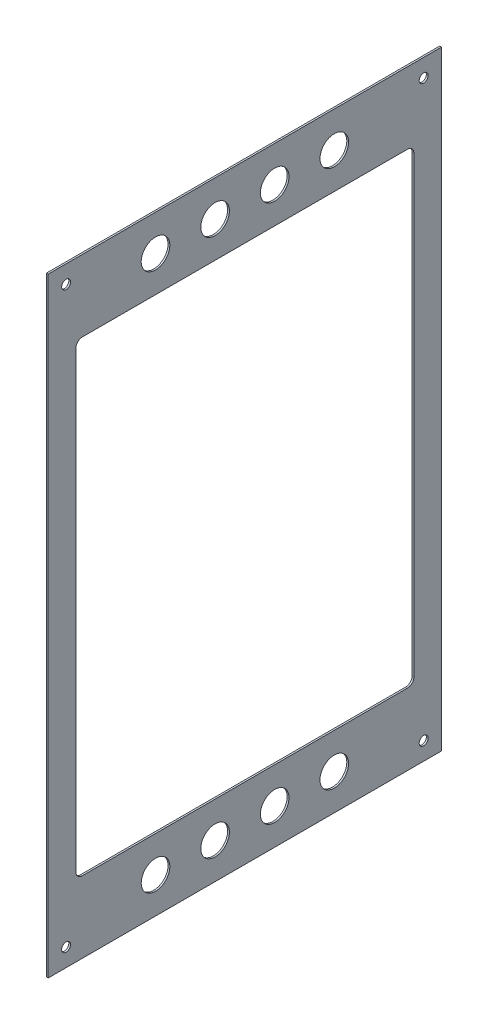
SolidWorks part; units mm, degrees
ref_plane "Front Plane" through (0, 0, 0) normal (1, 0, 0) x (0, 1, 0)
ref_plane "Top Plane" through (0, 0, 0) normal (0, 0, 1) x (0, 1, 0)
ref_plane "Right Plane" through (0, 0, 0) normal (0, 1, 0) x (-1, 0, 0)
sketch "Sketch1" plane through (0, 0, 0) normal (1, 0, 0) x (0, 1, 0)
  line L1 (-170.5, -110) -> (170.5, -110)
  line L2 (-170.5, -110) -> (-170.5, 110)
  line L3 (-170.5, 110) -> (170.5, 110)
  line L4 (170.5, -110) -> (170.5, 110)
  line L5 (-170.5, -110) -> (170.5, 110) construction
  line L6 (-170.5, 110) -> (170.5, -110) construction
  point P0 (0, 0)
  dimension "D1" = 341
  dimension "D2" = 220
extrude "Boss-Extrude1" add sketch "Sketch1" along normal blind 1
sketch "Sketch2" plane through (1, 0, 0) normal (1, 0, 0) x (0, 1, 0)
  line L8 (-170.5, 0) -> (170.5, 0) construction
  line L9 (-170.5, 110) -> (-170.5, -110) construction
  line L10 (170.5, -110) -> (170.5, 110) construction
  line L11 (150.5026, 110) -> (150.5026, -110) construction
  line L12 (-130.5026, 91.0027) -> (-130.5026, -91.0027)
  line L13 (-127.0027, -94.5026) -> (127.0027, -94.5026)
  line L14 (130.5026, -91.0027) -> (130.5026, 91.0027)
  line L15 (127.0027, 94.5026) -> (-127.0027, 94.5026)
  line L16 (-130.5026, 91.0027) -> (-130.5026, -91.0027)
  line L17 (-127.0027, -94.5026) -> (127.0027, -94.5026)
  line L18 (130.5026, -91.0027) -> (130.5026, 91.0027)
  line L19 (127.0027, 94.5026) -> (-127.0027, 94.5026)
  line L20 (170.5, 110) -> (-170.5, 110) construction
  line L21 (0, 110) -> (0, -110) construction
  line L22 (-170.5, -110) -> (170.5, -110) construction
  circle A0 centre (150.5026, 50) radius 8
  arc A1 (-127.0027, 94.5026) -> (-130.5026, 91.0027) centre (-127.0027, 91.0027) ccw
  arc A2 (-130.5026, -91.0027) -> (-127.0027, -94.5026) centre (-127.0027, -91.0027) ccw
  arc A3 (127.0027, -94.5026) -> (130.5026, -91.0027) centre (127.0027, -91.0027) ccw
  arc A4 (130.5026, 91.0027) -> (127.0027, 94.5026) centre (127.0027, 91.0027) ccw
  arc A5 (-127.0027, 94.5026) -> (-130.5026, 91.0027) centre (-127.0027, 91.0027) ccw
  arc A6 (-130.5026, -91.0027) -> (-127.0027, -94.5026) centre (-127.0027, -91.0027) ccw
  arc A7 (127.0027, -94.5026) -> (130.5026, -91.0027) centre (127.0027, -91.0027) ccw
  arc A8 (130.5026, 91.0027) -> (127.0027, 94.5026) centre (127.0027, 91.0027) ccw
  circle A11 centre (150.5026, 16.67) radius 8
  circle A12 centre (150.5026, -16.67) radius 8
  circle A13 centre (150.5026, -50) radius 8
  circle A14 centre (-150.5026, -50) radius 8
  circle A15 centre (-150.5026, -16.67) radius 8
  circle A16 centre (-150.5026, 16.67) radius 8
  circle A17 centre (-150.5026, 50) radius 8
  dimension "D3" = 16
  dimension "D4" = 50
  dimension "D2" = 20
  dimension "D5" = 16.67
  dimension "D1" = 0.5
extrude "Cut-Extrude1" cut sketch "Sketch2" against normal through all
sketch "Sketch3" plane through (1, 0, 0) normal (1, 0, 0) x (0, 1, 0)
  line L0 (0, 110) -> (0, -110) construction
  line L1 (170.5, 110) -> (-170.5, 110) construction
  line L2 (-170.5, -110) -> (170.5, -110) construction
  line L3 (0, -110) -> (170.5, 0) construction
  line L4 (170.5, -110) -> (170.5, 110) construction
  line L5 (170.5, 0) -> (-170.5, 0) construction
  line L6 (-170.5, 110) -> (-170.5, -110) construction
  circle A0 centre (-160.5, 100) radius 2.5
  circle A1 centre (160.5, 100) radius 2.5
  circle A2 centre (-160.5, -100) radius 2.5
  circle A3 centre (160.5, -100) radius 2.5
  point P16 (0, 0)
  dimension "D3" = 5
  dimension "D1" = 10
  dimension "D2" = 10
extrude "Cut-Extrude2" cut sketch "Sketch3" against normal through all
